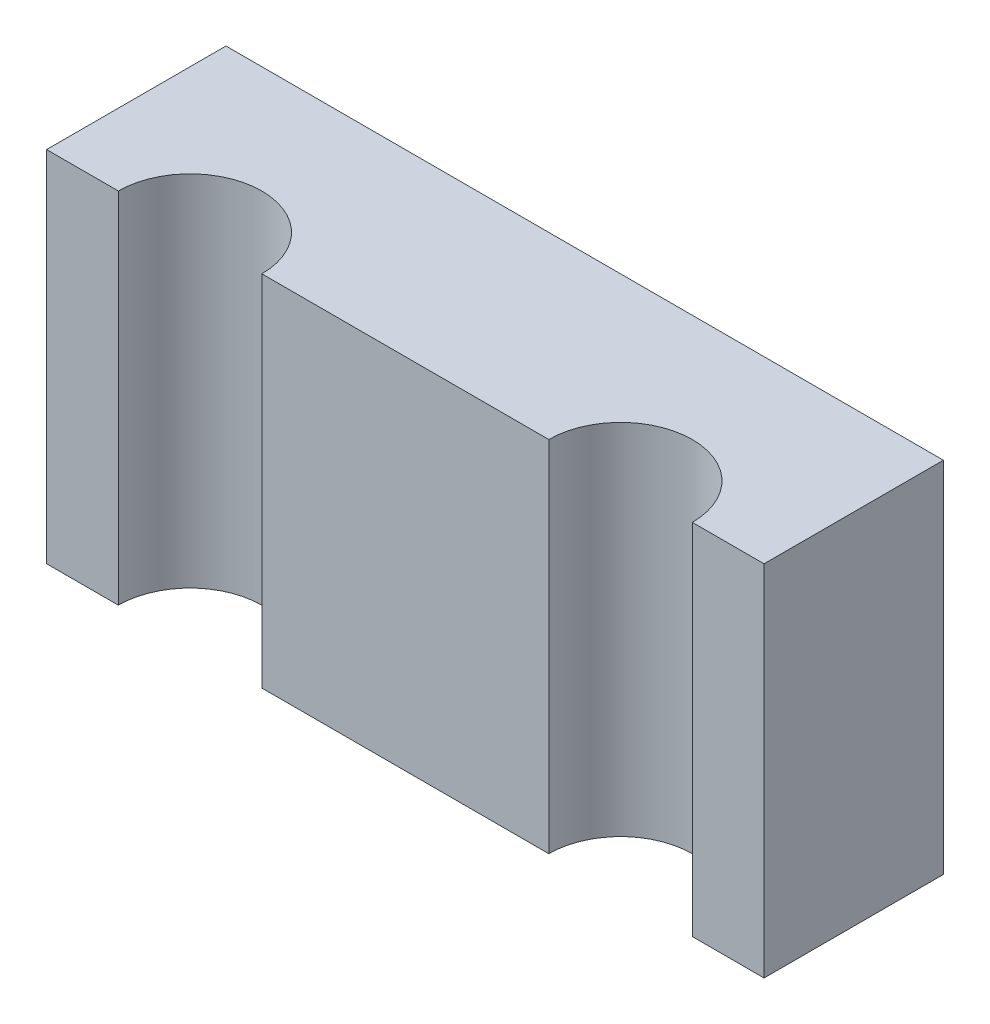
SolidWorks part; units mm, degrees
ref_plane "Ebene vorne" through (0, 0, 0) normal (0, 0, 1) x (1, 0, 0)
ref_plane "Ebene oben" through (0, 0, 0) normal (0, 1, 0) x (1, 0, 0)
ref_plane "Ebene rechts" through (0, 0, 0) normal (1, 0, 0) x (0, 0, -1)
sketch "Skizze1" plane through (0, 0, 0) normal (0, 0, 1) x (1, 0, 0)
  line L1 (0, 0) -> (100, 0)
  line L2 (0, 0) -> (0, 50)
  line L3 (0, 50) -> (100, 50)
  line L4 (100, 0) -> (100, 50)
  dimension "D1" = 100
  dimension "D2" = 50
extrude "Aufsatz-Linear austragen2" add sketch "Skizze1" along normal blind 25
sketch "Skizze4" plane through (0, 50, 0) normal (0, 1, 0) x (1, 0, 0)
  line L0 (100, -25) -> (0, -25) construction
  line L1 (0, -25) -> (0, 0) construction
  line L2 (100, -25) -> (100, 0) construction
  circle A0 centre (20, -25) radius 10
  circle A1 centre (80, -25) radius 10
  dimension "D1" = 20
  dimension "D2" = 20
  dimension "D3" = 20
  dimension "D4" = 20
extrude "Schnitt-Linear austragen3" cut sketch "Skizze4" against normal through all
sketch "Skizze5" plane through (0, 0, 0) normal (0, 0, -1) x (-1, 0, 0)
  line L0 (0, 50) -> (0, 0) construction
  line L1 (-5, 5) -> (-95, 5)
  line L2 (-5, 5) -> (-5, 45)
  line L3 (-5, 45) -> (-95, 45)
  line L4 (-95, 5) -> (-95, 45)
  line L5 (0, 0) -> (-100, 0) construction
  line L6 (-100, 0) -> (-100, 50) construction
  line L7 (-100, 50) -> (0, 50) construction
  dimension "D1" = 5
  dimension "D2" = 5
  dimension "D3" = 5
  dimension "D4" = 5
extrude "Schnitt-Linear austragen4" cut sketch "Skizze5" against normal blind 10
sketch "Skizze7" plane through (0, 0, 10) normal (0, 0, -1) x (-1, 0, 0)
  line L0 (-95, 5) -> (-5, 5) construction
  line L1 (-37.5, 5) -> (-62.5, 5)
  line L2 (-37.5, 5) -> (-37.5, 45)
  line L3 (-37.5, 45) -> (-62.5, 45)
  line L4 (-62.5, 5) -> (-62.5, 45)
  line L5 (-5, 45) -> (-95, 45) construction
  line L6 (-5, 5) -> (-5, 45) construction
  line L7 (-95, 45) -> (-95, 5) construction
  dimension "D1" = 32.5
  dimension "D2" = 32.5
extrude "Schnitt-Linear austragen5" cut sketch "Skizze7" against normal blind 10
fillet "Verrundung1" radius 10 1 edges at (37.5, 25, 10)
fillet "Verrundung2" radius 10 1 edges at (62.5, 25, 10)
sketch "Skizze8" plane through (0, 0, 10) normal (0, 0, -1) x (-1, 0, 0)
  line L0 (-95, 5) -> (-72.5, 5) construction
  line L1 (-95, 45) -> (-93, 45)
  line L2 (-95, 45) -> (-95, 5)
  line L3 (-95, 5) -> (-93, 5)
  line L4 (-93, 45) -> (-93, 5)
  dimension "D1" = 2
extrude "Schnitt-Linear austragen6" cut sketch "Skizze8" against normal blind 10
fillet "Verrundung3" radius 10 1 edges at (93, 25, 10)
